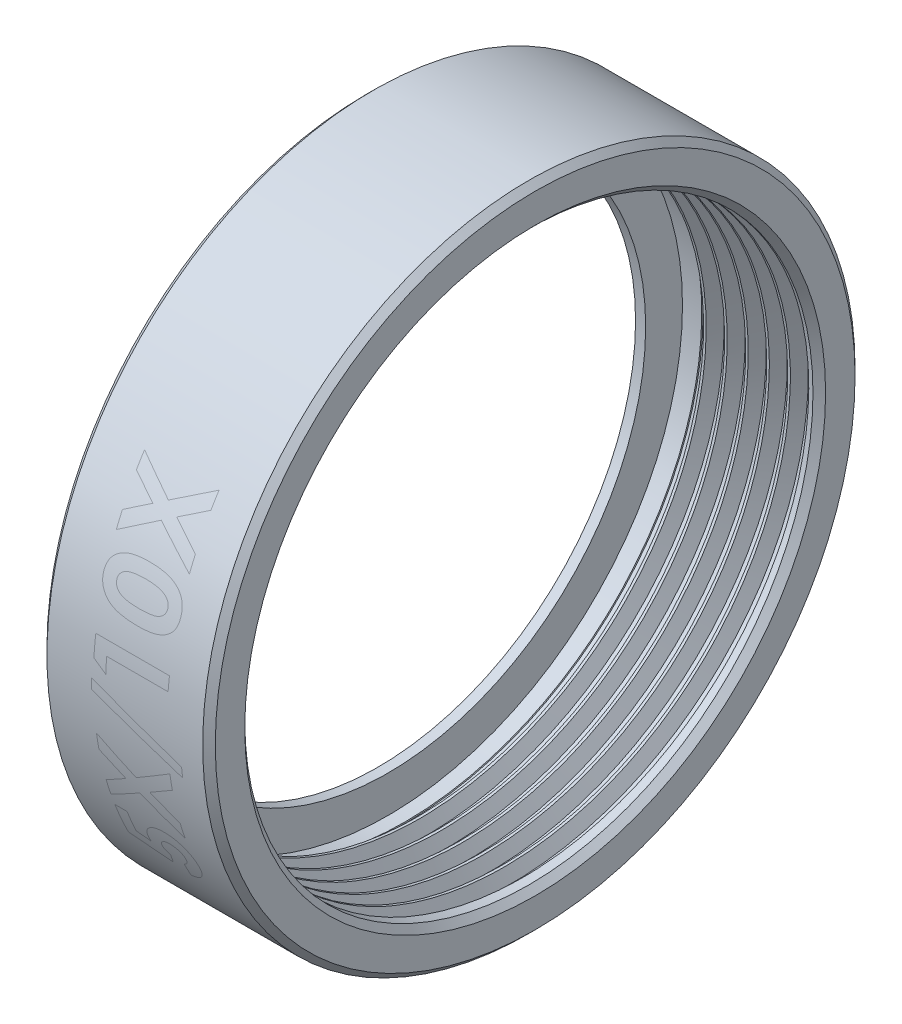
SolidWorks part; units mm, degrees
material "3.1325 (EN-AW 2017A)"
ref_plane "Front Plane" through (0, 0, 0) normal (0, 0, 1) x (1, 0, 0)
ref_plane "Top Plane" through (0, 0, 0) normal (0, 1, 0) x (1, 0, 0)
ref_plane "Right Plane" through (0, 0, 0) normal (1, 0, 0) x (0, 0, -1)
sketch "Sketch1" plane through (0, 0, 0) normal (0, 0, 1) x (1, 0, 0)
  line L0 (0, -13.15) -> (0, -15.2)
  line L1 (0.3, -15.5) -> (7.7, -15.5)
  line L2 (8, -15.2) -> (8, -13.8)
  line L4 (1, -14) -> (1, -12.25)
  line L5 (1, -12.25) -> (0.5196, -12.25)
  line L6 (35.4703, 0) -> (-35.4703, 0) construction
  line L7 (1, -14) -> (2, -14)
  line L8 (2, -14) -> (2, -13.5)
  line L9 (2, -13.5) -> (7.7, -13.5)
  line L10 (0, -15.2) -> (0.3, -15.5)
  line L11 (7.7, -15.5) -> (8, -15.2)
  line L12 (8, -13.8) -> (7.7, -13.5)
  line L13 (0.5196, -12.25) -> (0, -13.15)
  point P0 (0, -12.25)
  point P1 (0, -15.5)
  point P4 (8, -15.5)
  point P5 (8, -13.5)
  point P10 (0, 0)
  dimension "D1" = 31
  dimension "D2" = 24.5
  dimension "D3" = 8
  dimension "D4" = 7
  dimension "D5" = 1
  dimension "D6" = 0.5
  dimension "D7" = 27
  dimension "D8" = 0.9
  dimension "D9" = 30
revolve "Revolve1" add sketch "Sketch1" angle 360 about L6
cosmetic thread "Cosmetic Thread1" parameters "D2"=28
ref_plane "Plane2" through (0, 0, 15.5) normal (0, 0, 1) x (1, 0, 0)
sketch "Sketch3" plane through (0, 0, 15.5) normal (0, 0, 1) x (1, 0, 0)
  line L0 (6, -15.5) -> (6, 15.5) construction
  line L1 (8, -15.2) -> (8, 15.2) construction
  line L2 (0.3, -15.5) -> (7.7, -15.5) construction
  line L3 (7.7, 15.5) -> (0.3, 15.5) construction
  text T0 "<b>5X/10X</b>"
  point P4 (5.5, -15.5)
  point P7 (5.5, 15.5)
  dimension "D1" = 2
wrap "Wrap1" sketch "Sketch3" wrap type scribe source sketch "Sketch3" face at (7.7, 0, -15.5)
thread "Thread1" pitch 1 method cut profile "Thread Profile1" start angle 0, offset 0, length 0, pitch 1, diameter 27
ref_plane "Plane1" through (8, 0, 13.5) normal (0, -1, 0) x (0, 0, 1)
sketch "Thread Profile1" plane through (8, 0, 13.5) normal (0, -1, 0) x (0, 0, 1)
  line L0 (0, 0) -> (0, 1) construction
  line L11 (0, 0.875) -> (0, 0)
  line L12 (0, 0) -> (0.5413, 0.3125)
  line L13 (0.5413, 0.3125) -> (0.5413, 0.5625)
  line L15 (0.5413, 0.5625) -> (0, 0.875)
  line L17 (0.5413, 0.4375) -> (0, 0.4375) construction
  point P3 (0, 0)
  dimension "Pitch" = 1
  dimension "Profile_Angle" = 60
  dimension "Profile_Land" = 0.25
  dimension "Profile_Height" = 0.5413
